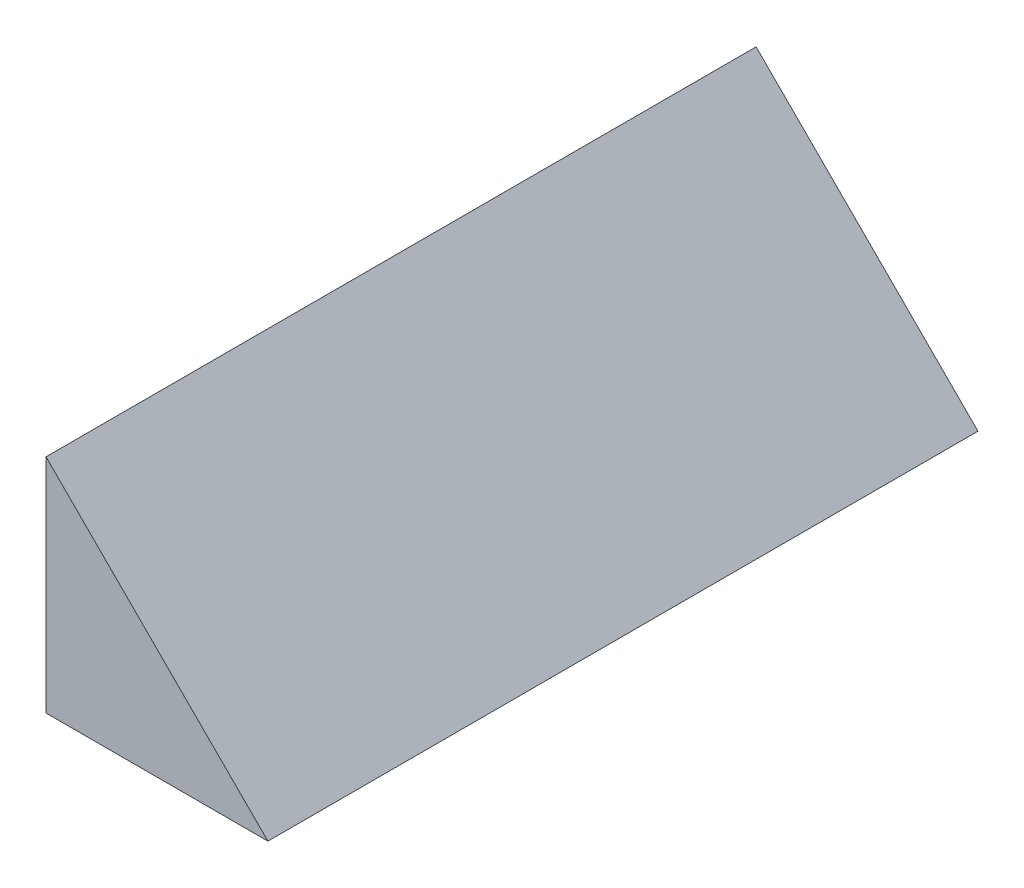
SolidWorks part; units mm, degrees
ref_plane "Front Plane" through (0, 0, 0) normal (0, 0, 1) x (1, 0, 0)
ref_plane "Top Plane" through (0, 0, 0) normal (0, 1, 0) x (1, 0, 0)
ref_plane "Right Plane" through (0, 0, 0) normal (1, 0, 0) x (0, 0, -1)
sketch "Sketch1" plane through (0, 0, 0) normal (0, 0, 1) x (1, 0, 0)
  line L0 (0, 0) -> (0, 0.25)
  line L1 (0, 0) -> (0.25, 0)
  line L5 (0, 0.25) -> (0.25, 0)
  dimension "D1" = 0.25
  dimension "D2" = 0.25
extrude "Boss-Extrude1" add sketch "Sketch1" along normal blind 0.8
equation "\"t\"= 0.25'thickness of the sheets"
equation "\"t_cf\" = 0.115'thickness of single carbon fiber layer"
equation "\"t_kapton\" = 0.025'thickness of single Kapton flex layer"
equation "\"t_fr4\" = 0.1'thickness of FR4 with copper layer"
equation "\"joint_flex\"= 0.1'Width of flextures gap"
equation "\"joint_flex_eff\"= 0.02'Width of flecture after castelation"
equation "\"joint_fold\"= 0.2'Width of folding joints for 90deg fold"
equation "\"gap_tolerance\"= 0.002'Width to have interfecence fit between carbon fiber inserts"
equation "\"assemble_angle\"= 90'Angle of assembly parts"
equation "\"link_lift\"= 0.5'Actuation linkage amplification for the lift motion"
equation "\"link_swing\"= 0.45'Actuation linkage amplification for the swing motion"
equation "\"D1@Boss-Extrude1\"=\"joint_fold\""
equation "\"D1@Sketch1\"=\"t\""
equation "\"D2@Sketch1\"=\"t\""
